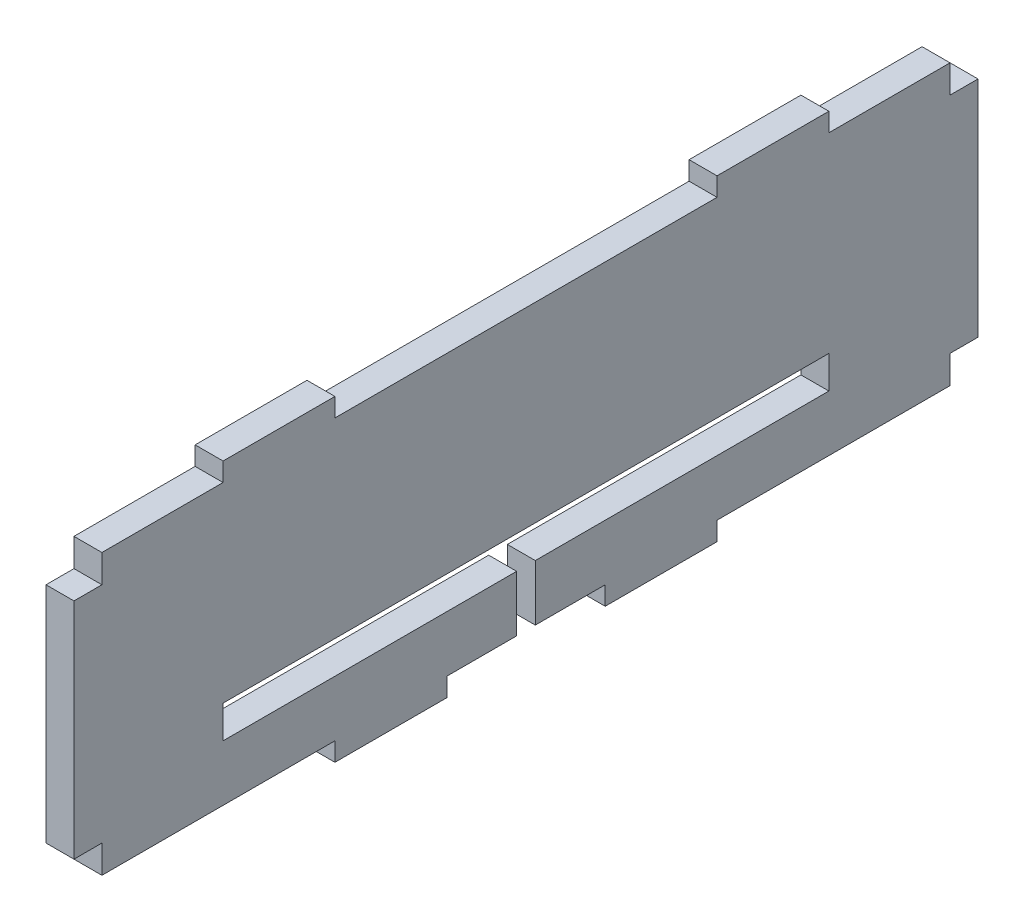
SolidWorks part; units mm, degrees
ref_plane "Front Plane" through (0, 0, 0) normal (0, 0, 1) x (1, 0, 0)
ref_plane "Top Plane" through (0, 0, 0) normal (0, 1, 0) x (1, 0, 0)
ref_plane "Right Plane" through (0, 0, 0) normal (1, 0, 0) x (0, 0, -1)
sketch "Sketch1" plane through (0, 0, 0) normal (1, 0, 0) x (0, 0, -1)
  line L0 (0, 0) -> (0, -32841.5669)
  line L1 (0, 0) -> (32841.5669, 0)
  line L2 (0, 5) -> (3, 5)
  line L3 (0, 0) -> (97, 0)
  line L4 (0, 0) -> (0, 34)
  line L5 (0, 34) -> (97, 34)
  line L6 (97, 0) -> (97, 34)
  line L11 (3, 5) -> (3, 2)
  line L12 (3, 2) -> (28, 2)
  line L13 (28, 2) -> (28, 0)
  line L14 (28, 0) -> (40, 0)
  line L15 (40, 0) -> (40, 2)
  line L16 (16, 8) -> (47.5, 8)
  line L17 (47.5, 8) -> (47.5, 2)
  line L18 (47.5, 2) -> (40, 2)
  line L19 (16, 8) -> (16, 11.5)
  line L20 (16, 11.5) -> (81, 11.5)
  line L21 (81, 11.5) -> (81, 8)
  line L22 (81, 8) -> (49.5, 8)
  line L23 (49.5, 8) -> (49.5, 2)
  line L24 (49.5, 2) -> (57, 2)
  line L25 (57, 2) -> (57, 0)
  line L26 (57, 0) -> (69, 0)
  line L27 (69, 0) -> (69, 2)
  line L28 (69, 2) -> (94, 2)
  line L29 (94, 2) -> (94, 5)
  line L30 (94, 5) -> (97, 5)
  line L31 (0, 29) -> (3, 29)
  line L32 (3, 29) -> (3, 32)
  line L33 (3, 32) -> (16, 32)
  line L34 (16, 32) -> (16, 34)
  line L35 (16, 34) -> (28, 34)
  line L36 (28, 34) -> (28, 32)
  line L37 (28, 32) -> (69, 32)
  line L38 (69, 32) -> (69, 34)
  line L39 (69, 34) -> (81, 34)
  line L40 (81, 34) -> (81, 32)
  line L41 (81, 32) -> (94, 32)
  line L42 (94, 32) -> (94, 29)
  line L43 (94, 29) -> (97, 29)
  dimension "D1" = 34
  dimension "D2" = 97
  dimension "D3" = 2
  dimension "D4" = 3
  dimension "D5" = 3
  dimension "D6" = 2
  dimension "D7" = 12
  dimension "D8" = 17
  dimension "D9" = 3
  dimension "D10" = 3
  dimension "D11" = 12
  dimension "D13" = 12
  dimension "D14" = 2
  dimension "D15" = 2
  dimension "D16" = 12
  dimension "D17" = 2
  dimension "D18" = 3
  dimension "D19" = 5
  dimension "D20" = 3
  dimension "D21" = 12
  dimension "D22" = 12
  dimension "D23" = 3.5
  dimension "D24" = 6
extrude "Boss-Extrude1" add sketch "Sketch1" along normal blind 3 contours L43 L42 L41 L40 L5 L38 L37 L36 L34 L33 L32 L31 L4 L2 L11 L12 L13 L3 L15 L18 L17 L16 L19 L20 L21 L22 L23 L24 L25 L27 L28 L29 L30 L6 region at (0, 17.6568, -48.5)
